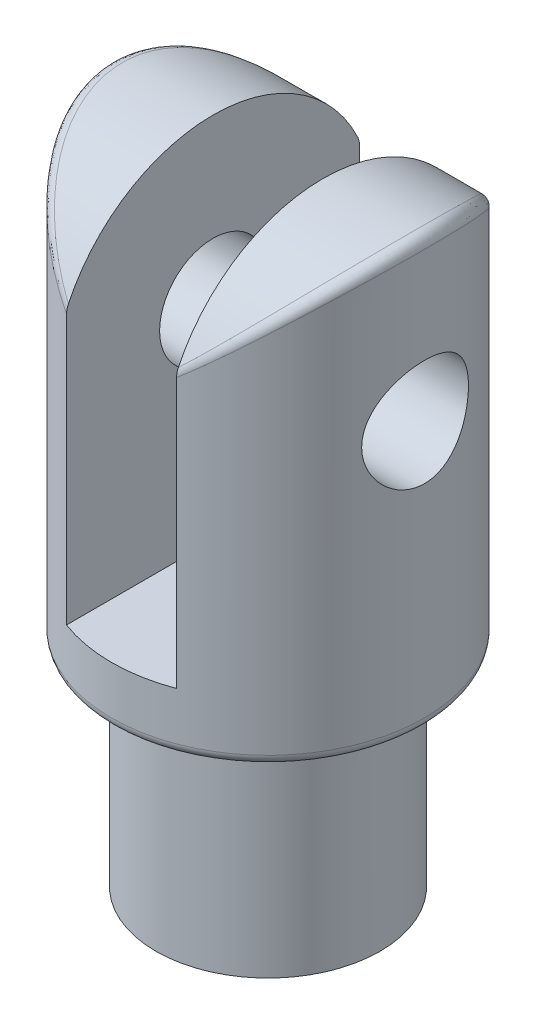
SolidWorks part; units mm, degrees
ref_plane "Front Plane" through (0, 0, 0) normal (0, 0, 1) x (1, 0, 0)
ref_plane "Top Plane" through (0, 0, 0) normal (0, 1, 0) x (1, 0, 0)
ref_plane "Right Plane" through (0, 0, 0) normal (1, 0, 0) x (0, 0, -1)
sketch "Sketch1" plane through (0, 0, 0) normal (0, 1, 0) x (1, 0, 0)
  circle A0 centre (0, 0) radius 14.65
  dimension "D1" = 29.3
extrude "Boss-Extrude1" add sketch "Sketch1" along normal blind 40
sketch "Sketch2" plane through (0, 0, 0) normal (0, 0, 1) x (1, 0, 0)
  line L0 (0, 43.4399) -> (0, -1.4888) construction
  line L1 (-5.15, 43.4399) -> (-5.15, 5.5)
  line L2 (5.15, 43.4399) -> (5.15, 5.5)
  line L3 (-5.15, 5.5) -> (5.15, 5.5)
  line L4 (-14.65, 0) -> (14.65, 0) construction
  line L5 (5.15, 43.4399) -> (5.15, -1.4888) construction
  line L6 (-5.15, 43.4399) -> (-5.15, -1.4888) construction
  line L7 (5.15, 43.4399) -> (-5.15, 43.4399)
  dimension "D1" = 5.15
  dimension "D3" = 5.5
  dimension "D2" = 5.15
extrude "Cut-Extrude1" cut sketch "Sketch2" against normal blind 19 and the other way blind 19 contours L7 L1 L3 L2
sketch "Sketch3" plane through (0, 0, 0) normal (1, 0, 0) x (0, 0, -1)
  line L3 (13.715, 40) -> (-13.715, 40) construction
  line L4 (-14.9266, 23.5181) -> (-17.1318, 45.7307)
  line L5 (-17.1318, 45.7307) -> (19.4486, 46.7846)
  line L6 (19.4486, 46.7846) -> (14.1842, 29.8795)
  arc A0 (14.1842, 29.8795) -> (-14.9266, 23.5181) centre (0, 25) ccw
  dimension "D1" = 30
extrude "Cut-Extrude2" cut sketch "Sketch3" against normal blind 19 and the other way blind 19
fillet "Fillet1" radius 1 2 edges at (-14.6207, 39.9714, -0.9265) (14.6178, 39.9686, -0.9702)
sketch "Sketch4" plane through (0, 0, 0) normal (1, 0, 0) x (0, 0, -1)
  line L0 (-14.65, 0) -> (14.65, 0) construction
  circle A0 centre (0, 25) radius 5
  dimension "D1" = 10
  dimension "D2" = 25
extrude "Cut-Extrude3" cut sketch "Sketch4" against normal blind 19 and the other way blind 19
fillet "Fillet2" radius 1 1 edges at (0, 0, 14.65)
sketch "Sketch5" plane through (0, 0, 0) normal (0, -1, 0) x (1, 0, 0)
  circle A0 centre (0, 0) radius 10.5
  dimension "D1" = 21
extrude "Boss-Extrude2" add sketch "Sketch5" along normal blind 20
